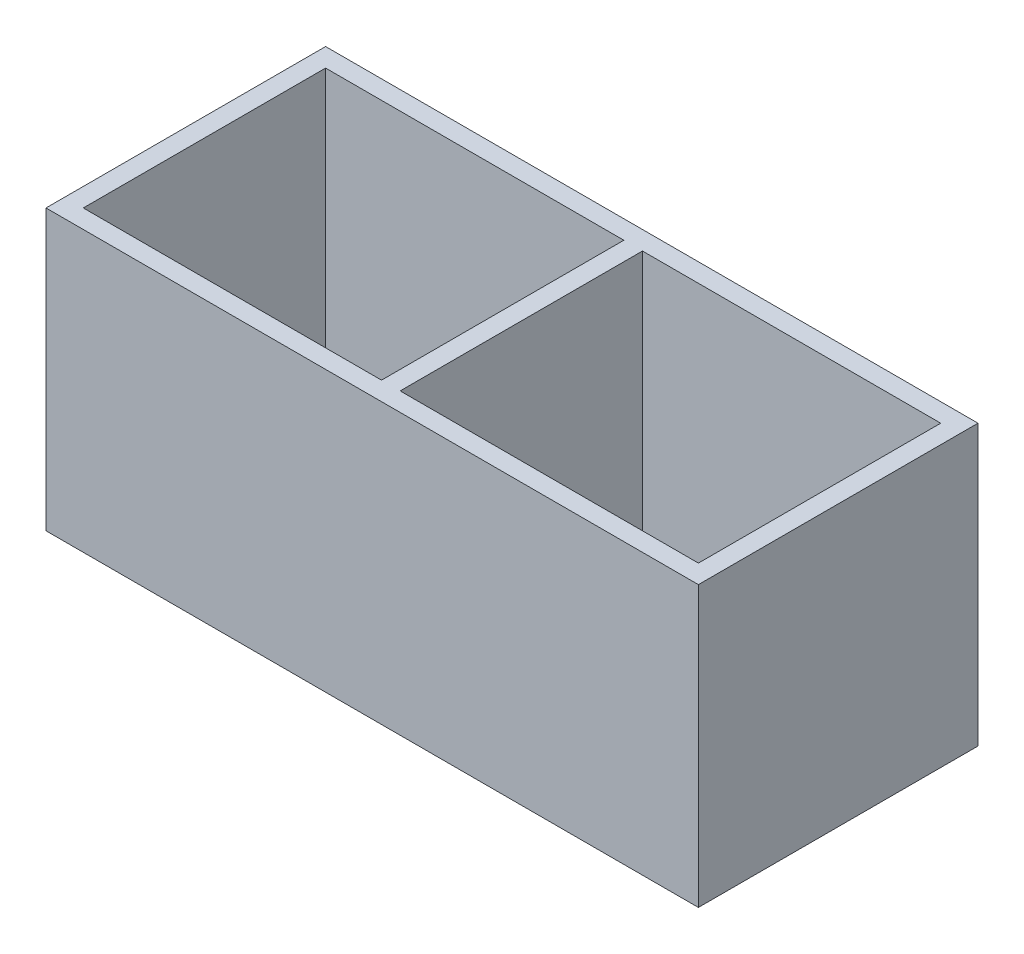
SolidWorks part; units mm, degrees
material "AISI 304"
ref_plane "前视基准面" through (0, 0, 0) normal (0, 0, 1) x (1, 0, 0)
ref_plane "上视基准面" through (0, 0, 0) normal (0, 1, 0) x (1, 0, 0)
ref_plane "右视基准面" through (0, 0, 0) normal (1, 0, 0) x (0, 0, -1)
ref_plane "InnerBottom" through (0, 0, 0) normal (0, 1, 0) x (1, 0, 0)
sketch "Circle" plane through (0, 0, 0) normal (0, 1, 0) x (1, 0, 0)
  line L0 (0, 0) -> (0, 200) construction
  dimension "R" = 200
ref_plane "InnerTop" through (0, 60, 0) normal (0, 1, 0) x (1, 0, 0)
ref_plane "SlotCenterV" through (0, 0, 0) normal (1, 0, 0) x (0, 0, -1)
ref_plane "SlotCenterH" through (0, 0, 0) normal (0, 0, 1) x (1, 0, 0)
ref_axis "CenterAxis" through (0, 0, -200) along (0, 1, 0)
sketch "STwoSlot" plane through (0, 0, 0) normal (0, 1, 0) x (1, 0, 0)
  line L0 (-32.1742, 0) -> (29.2905, 0) construction
  line L1 (0, 21.3687) -> (0, -19.6077) construction
  line L2 (-5, 4) -> (-5, -4)
  line L3 (-5, -4) -> (-7, -4)
  line L4 (-7, -4) -> (-7, -3)
  line L5 (-7, -3) -> (-10, -3)
  line L6 (-10, 3) -> (-7, 3)
  line L7 (-7, 3) -> (-7, 4)
  line L8 (-7, 4) -> (-5, 4)
  line L9 (5, -4) -> (7, -4)
  line L10 (7, -4) -> (7, -3)
  line L11 (7, -3) -> (10, -3)
  line L12 (10, 3) -> (7, 3)
  line L13 (7, 3) -> (7, 4)
  line L14 (7, 4) -> (5, 4)
  line L15 (5, 4) -> (5, -4)
  arc A0 (-10, -3) -> (-10, 3) centre (-10, 0) cw
  arc A1 (10, -3) -> (10, 3) centre (10, 0) ccw
  dimension "D4" = 3
  dimension "D1" = 8
  dimension "D2" = 2
  dimension "D3" = 3
  dimension "D5" = 10
sketch "STwoBase" plane through (0, 0, 0) normal (0, 1, 0) x (1, 0, 0)
  line L0 (0, 7.5) -> (0, -6.5) construction
  line L1 (-17.5, -7.5) -> (17.5, -7.5)
  line L2 (-17.5, -7.5) -> (-17.5, 7.5)
  line L3 (-17.5, 7.5) -> (17.5, 7.5)
  line L4 (17.5, -7.5) -> (17.5, 7.5)
  line L5 (-17.5, -7.5) -> (17.5, 7.5) construction
  line L6 (-17.5, 7.5) -> (17.5, -7.5) construction
  line L7 (-16.5, -6.5) -> (-0.5, -6.5)
  line L8 (-16.5, -6.5) -> (-16.5, 6.5)
  line L9 (-16.5, 6.5) -> (-0.5, 6.5)
  line L10 (16.5, -6.5) -> (16.5, 6.5)
  line L11 (-16.5, -6.5) -> (16.5, 6.5) construction
  line L12 (-16.5, 6.5) -> (16.5, -6.5) construction
  line L13 (-0.5, 6.5) -> (-0.5, -6.5)
  line L14 (0.5, 6.5) -> (0.5, -6.5)
  line L15 (0.5, 6.5) -> (16.5, 6.5)
  line L16 (0.5, -6.5) -> (16.5, -6.5)
  line L17 (0, 6.5) -> (0, -6.5) construction
  point P0 (0, 0)
  point P6 (0, 0)
  dimension "D1" = 35
  dimension "D5" = 1
  dimension "D2" = 15
  dimension "D3" = 1
  dimension "D4" = 1
extrude "FTwoBase" add sketch "STwoBase" along normal blind 15
sketch "SFiveSlotTP1" [suppressed] plane through (0, 0, 0) normal (0, 1, 0) x (1, 0, 0)
  line L0 (0, 21.9383) -> (0, -21.3523) construction
  line L1 (-37.6162, 0) -> (47.1378, 0) construction
  line L2 (-5.15, 11) -> (-5.15, 3)
  line L3 (-5.15, 3) -> (-7.55, 3)
  line L4 (-7.55, 3) -> (-7.55, 4)
  line L5 (-7.55, 4) -> (-10.55, 4)
  line L6 (-10.55, 10) -> (-7.55, 10)
  line L7 (-7.55, 10) -> (-7.55, 11)
  line L8 (-7.55, 11) -> (-5.15, 11)
  line L9 (-10.55, 7) -> (-5.15, 7) construction
  line L10 (7.55, 10) -> (7.55, 11)
  line L11 (10.55, 10) -> (7.55, 10)
  line L12 (7.55, 4) -> (10.55, 4)
  line L13 (7.55, 3) -> (7.55, 4)
  line L14 (5.15, 3) -> (7.55, 3)
  line L15 (5.15, 11) -> (5.15, 3)
  line L16 (7.55, 11) -> (5.15, 11)
  line L17 (-1.2, 7) -> (1.2, 7) construction
  line L18 (-1.2, 11.5) -> (1.2, 11.5)
  line L19 (-1.2, 11.5) -> (-1.2, 2.5)
  line L20 (-1.2, 2.5) -> (1.2, 2.5)
  line L21 (1.2, 11.5) -> (1.2, 2.5)
  line L22 (-7.2169, -4.1) -> (-2.7169, -11.8942)
  line L23 (-2.7169, -11.8942) -> (-4.7953, -13.0942)
  line L24 (-4.7953, -13.0942) -> (-9.2953, -5.3)
  line L25 (-9.2953, -5.3) -> (-7.2169, -4.1)
  line L26 (2.7169, -11.8942) -> (4.7953, -13.0942)
  line L27 (7.2169, -4.1) -> (2.7169, -11.8942)
  line L28 (4.7953, -13.0942) -> (9.2953, -5.3)
  line L29 (9.2953, -5.3) -> (7.2169, -4.1)
  line L30 (-8.2561, -4.7) -> (-3.7561, -12.4942) construction
  line L31 (-6.35, 11) -> (-6.35, 3) construction
  line L32 (6.35, 11) -> (6.35, 3) construction
  arc A0 (-10.55, 4) -> (-10.55, 10) centre (-10.55, 7) cw
  arc A1 (10.55, 4) -> (10.55, 10) centre (10.55, 7) ccw
  dimension "D4" = 3
  dimension "D1" = 8
  dimension "T3" = 2.4
  dimension "D3" = 3
  dimension "B1" = 9
  dimension "T1" = 2.4
  dimension "D7" = 7
  dimension "T2" = 2.4
  dimension "B2" = 9
  dimension "D12" = 60
  dimension "A" = 11.1
  dimension "F" = 9.5
  dimension "F2" = 12.7
sketch "SFiveBaseTP1" [suppressed] plane through (0, 0, 0) normal (0, 1, 0) x (1, 0, 0)
  line L0 (0, 29.2892) -> (0, -26.2802) construction
  line L1 (-17.5, 15) -> (17.5, 15)
  line L2 (17.5, 15) -> (17.5, 0)
  line L3 (17.5, 0) -> (7.5, -17.3205)
  line L4 (7.5, -17.3205) -> (-7.5, -17.3205)
  line L5 (-7.5, -17.3205) -> (-17.5, 0)
  line L6 (-17.5, 0) -> (-17.5, 15)
  line L8 (-16.3453, 0) -> (-6.9226, -16.3205)
  line L9 (-16.5, 14) -> (-3.75, 14)
  line L10 (-16.5, 14) -> (-16.5, 1)
  line L11 (-16.5, 1) -> (-3.75, 1)
  line L12 (16.5, 14) -> (16.5, 1)
  line L13 (-6.9226, -16.3205) -> (-0.5, -16.3205)
  line L14 (-0.5, -16.3205) -> (-0.5, 0)
  line L15 (-0.5, 0) -> (-16.3453, 0)
  line L16 (0.5, 0) -> (0.5, -16.3205)
  line L17 (0.5, -16.3205) -> (6.9226, -16.3205)
  line L18 (6.9226, -16.3205) -> (16.3453, 0)
  line L19 (16.3453, 0) -> (0.5, 0)
  line L20 (-3.75, 14) -> (-3.75, 1)
  line L21 (-2.75, 14) -> (-2.75, 1)
  line L22 (2.75, 14) -> (2.75, 1)
  line L23 (3.75, 14) -> (3.75, 1)
  line L24 (-2.75, 14) -> (2.75, 14)
  line L25 (3.75, 14) -> (16.5, 14)
  line L26 (-2.75, 1) -> (2.75, 1)
  line L27 (3.75, 1) -> (16.5, 1)
  dimension "D1" = 35
  dimension "D2" = 60
  dimension "D3" = 15
  dimension "D4" = 15
  dimension "D5" = 1
  dimension "D6" = 1
  dimension "D7" = 1
  dimension "D8" = 1
  dimension "D9" = 1
  dimension "D10" = 1
  dimension "D11" = 13
  dimension "D12" = 1
  dimension "D13" = 1
  dimension "D14" = 1
  dimension "D15" = 1
  dimension "D16" = 7.5
extrude "FFiveBaseTP1" [suppressed] add sketch "SFiveBaseTP1" along normal blind 15
sketch "SThreeSlot" [suppressed] plane through (0, 0, 0) normal (0, 1, 0) x (1, 0, 0)
  line L0 (-38.3697, 0) -> (49.7492, 0) construction
  line L1 (0, 31.5127) -> (0, -28.5949) construction
  line L2 (-9.2953, -5.3) -> (-4.7953, -13.0942)
  line L3 (-1.2, 11.5) -> (1.2, 11.5)
  line L4 (-1.2, 11.5) -> (-1.2, 2.5)
  line L5 (-1.2, 2.5) -> (1.2, 2.5)
  line L6 (1.2, 11.5) -> (1.2, 2.5)
  line L7 (-9.2953, -5.3) -> (-7.2169, -4.1)
  line L8 (-4.7953, -13.0942) -> (-2.7169, -11.8942)
  line L9 (-7.2169, -4.1) -> (-2.7169, -11.8942)
  line L10 (2.7169, -11.8942) -> (7.2169, -4.1)
  line L11 (2.7169, -11.8942) -> (4.7953, -13.0942)
  line L12 (7.2169, -4.1) -> (9.2953, -5.3)
  line L13 (4.7953, -13.0942) -> (9.2953, -5.3)
  line L14 (-1.2, 7) -> (1.2, 7) construction
  line L15 (-8.2561, -4.7) -> (-3.7561, -12.4942) construction
  dimension "B1" = 9
  dimension "T1" = 2.4
  dimension "T2" = 2.4
  dimension "B2" = 9
  dimension "F" = 9.5
  dimension "D1" = 60
  dimension "D2" = 11.1
  dimension "D3" = 7
sketch "SThreeBase" [suppressed] plane through (0, 0, 0) normal (0, 1, 0) x (1, 0, 0)
  line L0 (-19.047, 0) -> (-7.5, -20)
  line L1 (-7.5, -20) -> (7.5, -20)
  line L2 (7.5, -20) -> (19.047, 0)
  line L3 (19.047, 0) -> (5, 0)
  line L4 (5, 0) -> (5, 15)
  line L5 (5, 15) -> (-5, 15)
  line L6 (-5, 15) -> (-5, 0)
  line L7 (-19.047, 0) -> (-5, 0)
  line L8 (0, 24.0859) -> (0, -25.4306) construction
  line L9 (0, 31.5127) -> (0, -28.5949) construction
  line L11 (4, 0) -> (4, 14)
  line L12 (4, 14) -> (-4, 14)
  line L13 (-4, 14) -> (-4, 0)
  line L14 (-17.315, -1) -> (-4, -1)
  line L15 (-17.315, -1) -> (-6.9226, -19)
  line L16 (-6.9226, -19) -> (-0.5, -19)
  line L17 (6.9226, -19) -> (17.315, -1)
  line L18 (17.315, -1) -> (4, -1)
  line L19 (-4, -1) -> (-0.5, -1)
  line L20 (-4, 0) -> (4, 0)
  line L21 (-0.5, -1) -> (-0.5, -19)
  line L22 (-4, 14) -> (-4, -1) construction
  line L23 (4, -1) -> (4, 14) construction
  line L24 (0.5, -1) -> (0.5, -19)
  line L25 (0.5, -1) -> (4, -1)
  line L26 (0.5, -19) -> (6.9226, -19)
  line L28 (-6.9226, -19) -> (6.9226, -19) construction
  dimension "D3" = 15
  dimension "D6" = 1
  dimension "D7" = 1
  dimension "D2" = 15
  dimension "D1" = 10
  dimension "D4" = 20
  dimension "D5" = 60
extrude "FThreeBase" [suppressed] add sketch "SThreeBase" along normal blind 15
sketch "SUsbSlot" [suppressed] plane through (0, 0, 0) normal (0, 1, 0) x (1, 0, 0)
  line L0 (0, 4.2432) -> (0, -4.6578) construction
  line L2 (-2.5, -6) -> (2.5, -6)
  line L3 (-2.5, -6) -> (-2.5, 6)
  line L4 (-2.5, 6) -> (2.5, 6)
  line L5 (2.5, -6) -> (2.5, 6)
  line L6 (-2.5, -6) -> (2.5, 6) construction
  line L7 (-2.5, 6) -> (2.5, -6) construction
  point P3 (0, 0)
  dimension "UsbL" = 12
  dimension "UsbKd" = 5
sketch "SUsbBase" [suppressed] plane through (0, 0, 0) normal (0, 1, 0) x (1, 0, 0)
  line L1 (-5, -9) -> (5, -9)
  line L2 (-5, -9) -> (-5, 9)
  line L3 (-5, 9) -> (5, 9)
  line L4 (5, -9) -> (5, 9)
  line L5 (-5, -9) -> (5, 9) construction
  line L6 (-5, 9) -> (5, -9) construction
  line L7 (-4, 8) -> (4, 8)
  line L8 (4, -8) -> (4, 8)
  line L9 (-4, -8) -> (4, -8)
  line L10 (-4, -8) -> (-4, 8)
  dimension "D1" = 10
  dimension "D2" = 18
extrude "FUsbBase" [suppressed] add sketch "SUsbBase" along normal blind 15
equation "\"SlotL\"= 9"
equation "\"SlotKD\"= 2.4"
equation "\"B1@SFiveSlotTP1\"=\"SlotL\""
equation "\"B2@SFiveSlotTP1\"=\"SlotL\""
equation "\"T1@SFiveSlotTP1\"=\"SlotKD\""
equation "\"T3@SFiveSlotTP1\"=\"SlotKD\""
equation "\"T2@SFiveSlotTP1\"=\"SlotKD\""
equation "\"T1@SThreeSlot\"=\"SlotKD\""
equation "\"T2@SThreeSlot\"=\"SlotKD\""
equation "\"B1@SThreeSlot\"=\"SlotL\""
equation "\"B2@SThreeSlot\"=\"SlotL\""
equation "\"BaseTn\"= 1"
equation "\"D5@SFiveBaseTP1\"=\"BaseTn\""
equation "\"D6@SFiveBaseTP1\"=\"BaseTn\""
equation "\"D7@SFiveBaseTP1\"=\"BaseTn\""
equation "\"D8@SFiveBaseTP1\"=\"BaseTn\""
equation "\"D9@SFiveBaseTP1\"=\"BaseTn\""
equation "\"D10@SFiveBaseTP1\"=\"BaseTn\""
equation "\"D12@SFiveBaseTP1\"=\"BaseTn\""
equation "\"D13@SFiveBaseTP1\"=\"BaseTn\""
equation "\"D5@STwoBase\"=\"BaseTn\""
equation "\"D3@STwoBase\"=\"BaseTn\""
equation "\"D4@STwoBase\"=\"BaseTn\""
equation "\"BaseH\"= 15"
equation "\"D1@FTwoBase\"=\"BaseH\""
equation "\"D1@FFiveBaseTP1\"=\"BaseH\""
equation "\"D6@SThreeBase\"=\"BaseTn\""
equation "\"D1@FThreeBase\"=\"BaseH\""
equation "\"D7@SThreeBase\"=\"BaseTn\""
equation "\"D3@SUsbBase\"=\"BaseTn\""
equation "\"D1@FUsbBase\"=\"BaseH\""
equation "\"D14@SFiveBaseTP1\"=\"BaseTn\""
equation "\"D15@SFiveBaseTP1\"=\"BaseTn\""
